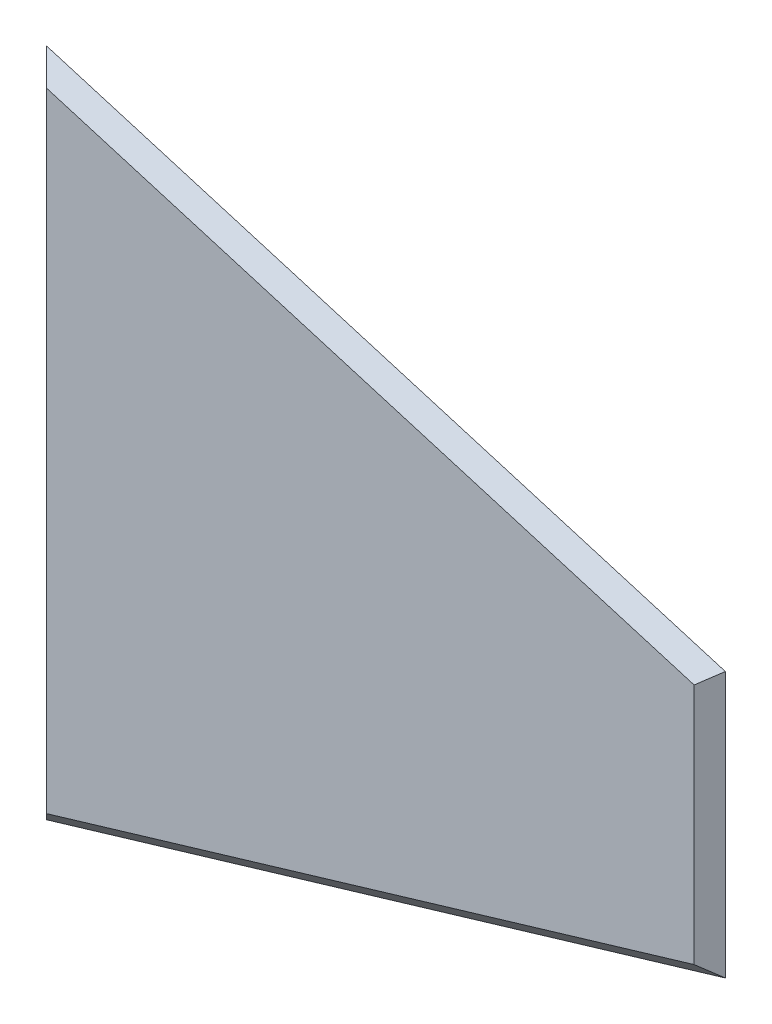
SolidWorks part; units mm, degrees
ref_plane "Ebene vorne" through (0, 0, 0) normal (0, 0, 1) x (1, 0, 0)
ref_plane "Ebene oben" through (0, 0, 0) normal (0, 1, 0) x (1, 0, 0)
ref_plane "Ebene rechts" through (0, 0, 0) normal (1, 0, 0) x (0, 0, -1)
sketch "Skizze1" plane through (0, 0, 0) normal (0, 0, 1) x (1, 0, 0)
  line L0 (-655.2882, 0) -> (689.2934, 0) construction
  line L1 (0, 379.1113) -> (0, -337.7537) construction
  line L2 (-434.7143, -214.6) -> (-434.7143, 214.6)
  line L3 (-434.7143, 214.6) -> (0, 85)
  line L4 (0, 85) -> (0, -85)
  line L6 (-434.7143, -214.6) -> (0, -85)
  point P10 (0, 0)
  point P11 (-434.7143, 0)
  dimension "D1" = 429.2
  dimension "D2" = 170
extrude "Aufsatz-Linear austragen1" add sketch "Skizze1" along normal blind 10
chamfer "Fase1" distance 10 angle 45 4 edges at (-434.7143, 0, 10) (-217.3572, 149.8, 10) (0, 0, 10) (-217.3572, -149.8, 10)
